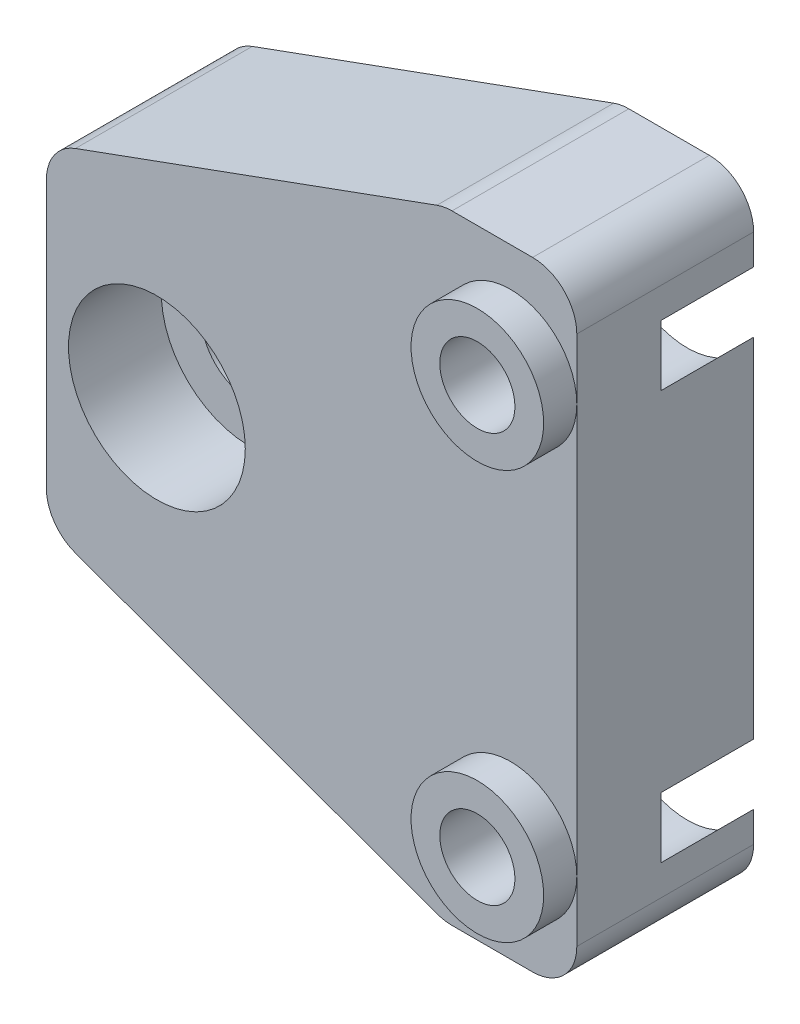
SolidWorks part; units mm, degrees
ref_plane "Plan de face" through (0, 0, 0) normal (0, 0, 1) x (1, 0, 0)
ref_plane "Plan de dessus" through (0, 0, 0) normal (0, 1, 0) x (1, 0, 0)
ref_plane "Plan de droite" through (0, 0, 0) normal (1, 0, 0) x (0, 0, -1)
sketch "Esquisse1" plane through (0, 0, 0) normal (0, 0, 1) x (1, 0, 0)
  line L1 (-8, 14) -> (16, 14)
  line L2 (-8, 14) -> (-8, -14)
  line L3 (-8, -14) -> (16, -14)
  line L4 (16, 14) -> (16, -14)
  dimension "D1" = 28
  dimension "D2" = 24
  dimension "D3" = 14
  dimension "D4" = 8
extrude "Boss.-Extru.1" add sketch "Esquisse1" along normal blind 8
sketch "Esquisse2" plane through (0, 0, 8) normal (0, 0, 1) x (1, 0, 0)
  line L0 (-8, 14) -> (-8, -14) construction
  line L1 (16, 14) -> (-8, 14) construction
  circle A0 centre (-3, 0) radius 2.2
  dimension "D1" = 4.4
  dimension "D2" = 5
  dimension "D3" = 14
extrude "Enlèv. mat.-Extru.1" cut sketch "Esquisse2" against normal through all
sketch "Esquisse3" plane through (0, 0, 8) normal (0, 0, 1) x (1, 0, 0)
  circle A0 centre (-3, 0) radius 4
  circle A1 centre (-3, 0) radius 2.2 construction
  dimension "D1" = 8
extrude "Enlèv. mat.-Extru.2" cut sketch "Esquisse3" against normal blind 4.2
sketch "Esquisse4" plane through (0, 0, 8) normal (0, 0, 1) x (1, 0, 0)
  line L0 (16, -14) -> (16, 14) construction
  circle A0 centre (13, 9.25) radius 1.7
  circle A1 centre (13, -9.25) radius 1.7
  dimension "D2" = 3.4
  dimension "D3" = 3.4
  dimension "D1" = 18.5
  dimension "D4" = 3
  dimension "D5" = 3
  dimension "D6" = 9.25
extrude "Enlèv. mat.-Extru.3" cut sketch "Esquisse4" against normal through all
sketch "Esquisse5" plane through (0, 0, 0) normal (0, 0, -1) x (-1, 0, 0)
  circle A0 centre (-13, 9.25) radius 3.3
  circle A1 centre (-13, -9.25) radius 3.3
  dimension "D1" = 6.6
  dimension "D2" = 6.6
extrude "Enlèv. mat.-Extru.6" cut sketch "Esquisse5" against normal blind 4.2
sketch "Esquisse6" plane through (0, 0, 4.2) normal (0, 0, -1) x (-1, 0, 0)
  circle A0 centre (-13, 9.25) radius 1.7
  circle A1 centre (-13, -9.25) radius 1.7
extrude "Boss.-Extru.2" add sketch "Esquisse6" against normal blind 1
chamfer "Chanfrein1" distance 18 angle 20 2 edges at (-8, -14, 4) (-8, 14, 4) first distance on face at (4, -14, 4) first distance on face at (4, 14, 4)
fillet "Congé1" radius 2 6 edges at (10, -14, 4) (16, -14, 4) (16, 14, 4) (10, 14, 4) (-8, -7.4485, 4) (-8, 7.4485, 4)
sketch "Esquisse7" plane through (0, 0, 8) normal (0, 0, 1) x (1, 0, 0)
  circle A0 centre (13, 9.25) radius 1.7
  circle A1 centre (13, -9.25) radius 1.7
  circle A2 centre (13, -9.25) radius 3
  circle A3 centre (13, 9.25) radius 3
extrude "Boss.-Extru.3" add sketch "Esquisse7" along normal blind 1.5
